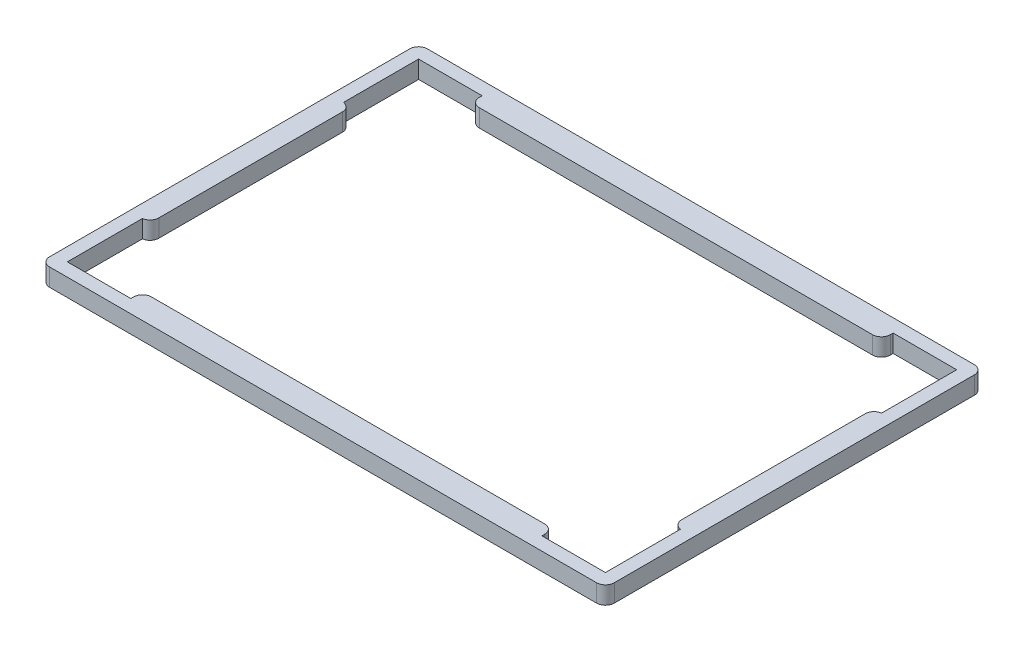
SolidWorks part; units mm, degrees
ref_plane "Front Plane" through (0, 0, 0) normal (0, 0, 1) x (1, 0, 0)
ref_plane "Top Plane" through (0, 0, 0) normal (0, 1, 0) x (1, 0, 0)
ref_plane "Right Plane" through (0, 0, 0) normal (1, 0, 0) x (0, 0, -1)
sketch "Sketch2" plane through (0, 0, 0) normal (0, 1, 0) x (1, 0, 0)
  line L1 (63.88, -42.74) -> (-63.88, -42.74)
  line L2 (63.88, -42.74) -> (63.88, 42.74)
  line L3 (63.88, 42.74) -> (-63.88, 42.74)
  line L4 (-63.88, -42.74) -> (-63.88, 42.74)
  line L5 (63.88, -42.74) -> (-63.88, 42.74) construction
  line L6 (63.88, 42.74) -> (-63.88, -42.74) construction
  line L7 (60.88, -39.74) -> (-60.88, -39.74)
  line L8 (60.88, -39.74) -> (60.88, 39.74)
  line L9 (60.88, 39.74) -> (-60.88, 39.74)
  line L10 (-60.88, -39.74) -> (-60.88, 39.74)
  line L11 (60.88, -39.74) -> (-60.88, 39.74) construction
  line L12 (60.88, 39.74) -> (-60.88, -39.74) construction
  line L13 (59.15, -22.75) -> (-59.15, -22.75)
  line L14 (59.15, -22.75) -> (59.15, 22.75)
  line L15 (59.15, 22.75) -> (-59.15, 22.75)
  line L16 (-59.15, -22.75) -> (-59.15, 22.75)
  line L17 (59.15, -22.75) -> (-59.15, 22.75) construction
  line L18 (59.15, 22.75) -> (-59.15, -22.75) construction
  line L19 (-59.15, 22.75) -> (-60.88, 22.75)
  line L20 (-59.15, 22.75) -> (-59.15, -22.75)
  line L21 (-59.15, -22.75) -> (-60.88, -22.75)
  line L22 (-60.88, 22.75) -> (-60.88, -22.75)
  line L23 (59.15, 22.75) -> (60.88, 22.75)
  line L24 (59.15, 22.75) -> (59.15, -22.75)
  line L25 (59.15, -22.75) -> (60.88, -22.75)
  line L26 (60.88, 22.75) -> (60.88, -22.75)
  line L27 (46.5, -37.09) -> (-46.5, -37.09)
  line L28 (46.5, -37.09) -> (46.5, 37.09)
  line L29 (46.5, 37.09) -> (-46.5, 37.09)
  line L30 (-46.5, -37.09) -> (-46.5, 37.09)
  line L31 (46.5, -37.09) -> (-46.5, 37.09) construction
  line L32 (46.5, 37.09) -> (-46.5, -37.09) construction
  line L33 (-46.5, 37.09) -> (46.5, 37.09)
  line L34 (-46.5, 37.09) -> (-46.5, 39.74)
  line L35 (-46.5, 39.74) -> (46.5, 39.74)
  line L36 (46.5, 37.09) -> (46.5, 39.74)
  line L37 (-46.5, -37.09) -> (46.5, -37.09)
  line L38 (-46.5, -37.09) -> (-46.5, -39.74)
  line L39 (-46.5, -39.74) -> (46.5, -39.74)
  line L40 (46.5, -37.09) -> (46.5, -39.74)
  point P0 (0, 0)
  point P6 (0, 0)
  point P11 (0, 0)
  point P20 (0, 0)
  dimension "D1" = 85.48
  dimension "D2" = 127.76
  dimension "D3" = 3
  dimension "D4" = 3
  dimension "D5" = 45.5
  dimension "D6" = 118.3
  dimension "D7" = 93
  dimension "D8" = 74.18
extrude "Boss-Extrude1" add sketch "Sketch2" along normal blind 4 contours L4 L1 L2 L3 L7 L10 L9 L8 | L21 L16 L19 L10 | L29 L36 L9 L34 | L14 L25 L8 L23 | L40 L27 L38 L7 region at (0, 0, 41.2028) region at (0, 0, 38.415) region at (60.015, 0, 0) region at (-60.015, 0, 0) region at (0, 0, -38.415)
fillet "Fillet1" radius 2 12 edges at (46.5, 2, 37.09) (59.15, 2, 22.75) (59.15, 2, -22.75) (46.5, 2, -37.09) (-46.5, 2, -37.09) (-59.15, 2, -22.75) (-46.5, 2, 37.09) (-59.15, 2, 22.75) (-63.88, 2, 42.74) (-63.88, 2, -42.74) (63.88, 2, -42.74) (63.88, 2, 42.74)
equation "\"Border\"= 3"
equation "\"D3@Sketch2\"=\"Border\""
equation "\"D4@Sketch2\"=\"Border\""
